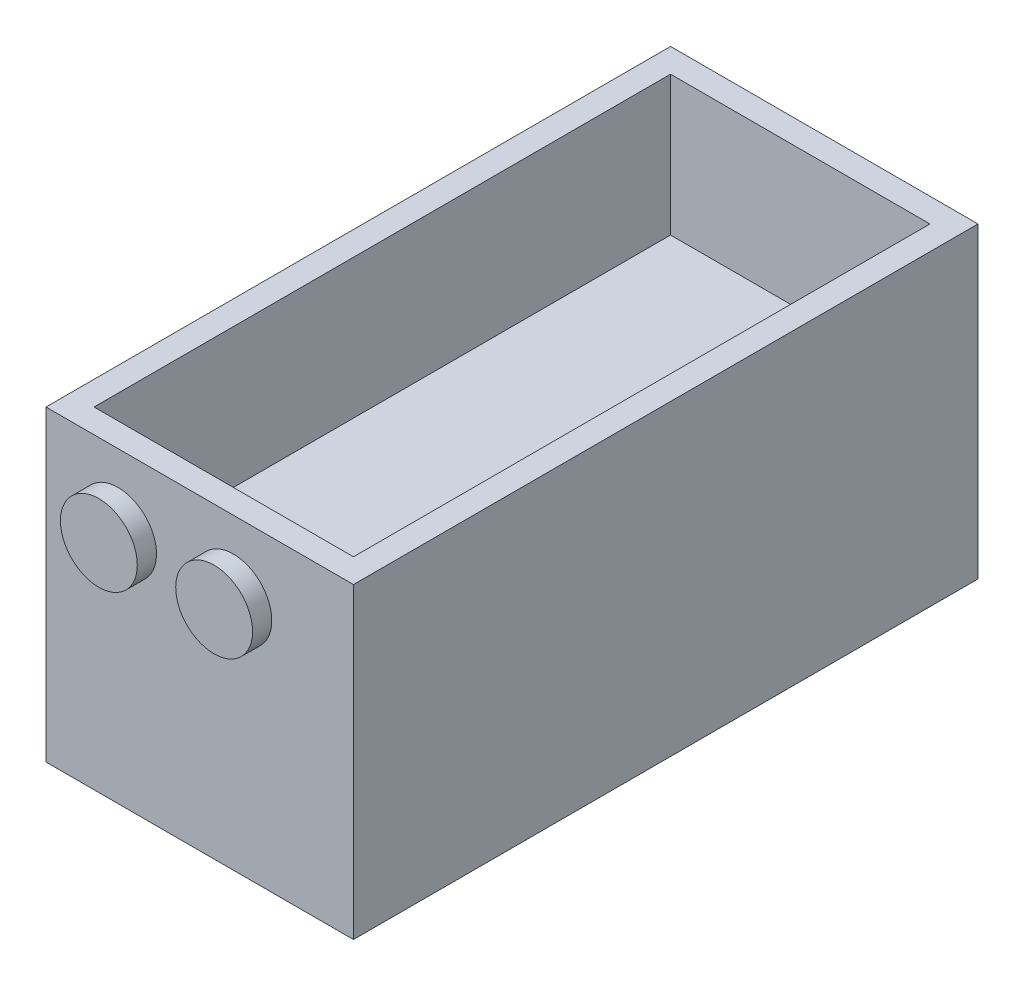
SolidWorks part; units mm, degrees
ref_plane "Front Plane" through (0, 0, 0) normal (0, 0, 1) x (1, 0, 0)
ref_plane "Top Plane" through (0, 0, 0) normal (0, 1, 0) x (1, 0, 0)
ref_plane "Right Plane" through (0, 0, 0) normal (1, 0, 0) x (0, 0, -1)
sketch "Sketch1" plane through (0, 0, 0) normal (0, 1, 0) x (1, 0, 0)
  line L1 (0, 0) -> (32, 0)
  line L2 (0, 0) -> (0, -65)
  line L3 (0, -65) -> (32, -65)
  line L4 (32, 0) -> (32, -65)
  dimension "D1" = 32
  dimension "D2" = 65
extrude "Boss-Extrude1" add sketch "Sketch1" along normal blind 32
shell "Shell1" thickness 2.5 removed face at (16, 32, 32.5)
shell "Shell2" thickness 2.5 removed face at (16, 0, 32.5)
sketch "Sketch2" plane through (0, 0, 65) normal (0, 0, 1) x (1, 0, 0)
  line L0 (0, 24.5) -> (32, 24.5) construction
  line L1 (0, 32) -> (0, 0) construction
  line L2 (32, 32) -> (32, 0) construction
  line L3 (0, 32) -> (32, 32) construction
  circle A0 centre (7.5, 24.5) radius 4
  circle A1 centre (19.5, 24.5) radius 4
  dimension "D4" = 8
  dimension "D1" = 7.5
  dimension "D2" = 7.5
  dimension "D3" = 12.5
extrude "Boss-Extrude2" add sketch "Sketch2" along normal blind 2
